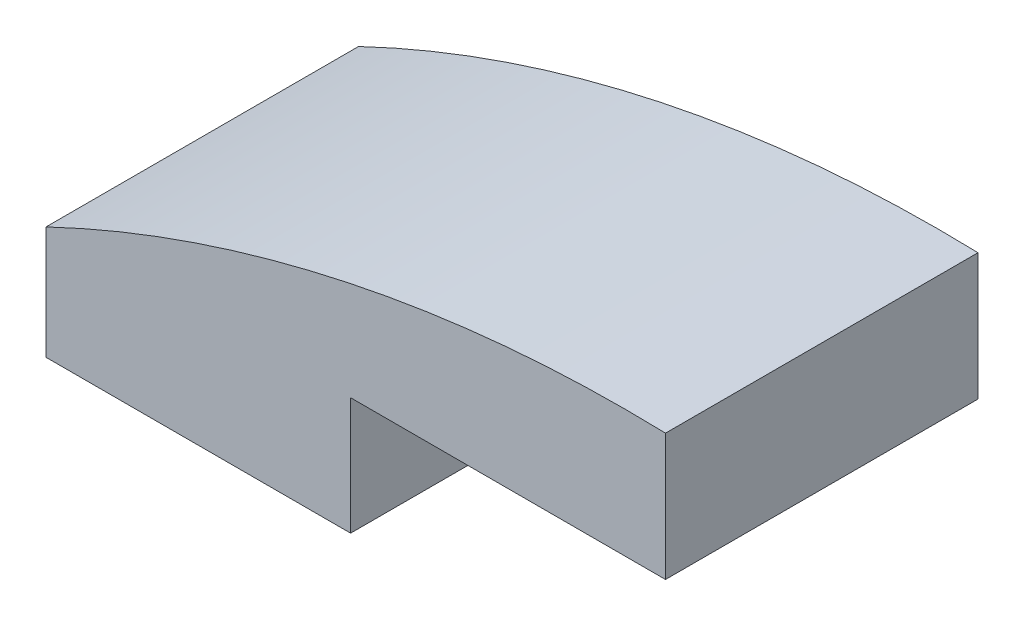
SolidWorks part; units mm, degrees
ref_plane "Front Plane" through (0, 0, 0) normal (0, 0, 1) x (1, 0, 0)
ref_plane "Top Plane" through (0, 0, 0) normal (0, 1, 0) x (1, 0, 0)
ref_plane "Right Plane" through (0, 0, 0) normal (1, 0, 0) x (0, 0, -1)
sketch "Sketch1" plane through (0, 0, 0) normal (0, 0, 1) x (1, 0, 0)
  line L0 (-7.9, -0.6252) -> (-7.9, 2.2297)
  line L12 (7.9, 5.5409) -> (7.9, 2.3409)
  line L15 (-0.2, -0.6252) -> (-7.9, -0.6252)
  line L17 (7.9, 2.3409) -> (-0.2, 2.3409)
  line L18 (-0.2, 2.3409) -> (-0.2, -0.6252)
  arc A0 (-7.9, 2.2297) -> (7.9, 5.5409) centre (6.7535, -28.3397) cw
  dimension "D3" = 3.2
extrude "Boss-Extrude1" add sketch "Sketch1" along normal mid plane 7.9
ref_plane "Plane1" through (0, -0.6252, 0) normal (0, -1, 0) x (-1, 0, 0)
shell "Shell1" thickness 1.2 removed face at (-4.05, -0.6252, 0) removed face at (3.85, 2.3409, 0)
ref_plane "Plane7" through (0, 2.3409, 0) normal (0, -1, 0) x (-1, 0, 0)
ref_plane "Plane8" [suppressed] through (0, 1.0372, 0) normal (0, -1, 0) x (-1, 0, 0)
sketch "Sketch7" [suppressed] plane through (0, 1.0372, 0) normal (0, -1, 0) x (-1, 0, 0)
  line L0 (7.9, 3.95) -> (0, -3.95)
  line L3 (7.9, 3.95) -> (7.9, -3.95)
  line L4 (7.9, -3.95) -> (0, -3.95)
extrude "Cut-Extrude4" [suppressed] cut sketch "Sketch7" against normal up to next
ref_plane "Plane9" through (0, 0, 0) normal (-1, 0, 0) x (0, 0, 1)
ref_plane "Plane10" through (0, 2.3409, 0) normal (0, -1, 0) x (-1, 0, 0)
sketch "Sketch8" plane through (0, 2.3409, 0) normal (0, -1, 0) x (-1, 0, 0)
  line L0 (-3.85, 3.95) -> (-3.85, -3.95) construction
  line L1 (0.2, 3.95) -> (-7.9, 3.95) construction
  line L2 (0.2, -3.95) -> (-7.9, -3.95) construction
  circle A0 centre (-3.85, 0) radius 2.3
  circle A1 centre (-3.85, 0) radius 2
  dimension "D1" = 4.6
  dimension "D2" = 4
extrude "Boss-Extrude2" add sketch "Sketch8" against normal up to next from offset 1.2
ref_plane "Plane11" through (0, -0.6252, 0) normal (0, -1, 0) x (-1, 0, 0)
sketch "Sketch9" plane through (0, -0.6252, 0) normal (0, -1, 0) x (-1, 0, 0)
  line L0 (1.4, 2.75) -> (6.7, -2.75) construction
  line L1 (6.7, 2.75) -> (1.4, -2.75) construction
  circle A0 centre (4.05, 0) radius 2.25
  circle A1 centre (4.05, 0) radius 2
  dimension "D1" = 4.5
  dimension "D2" = 4
extrude "Boss-Extrude3" add sketch "Sketch9" against normal up to next from offset 1.2
sketch "Sketch10" plane through (0, 0, -3.95) normal (0, 0, -1) x (-1, 0, 0)
  line L0 (-7.9, 2.3409) -> (-7.7606, 2.3409)
  line L1 (0.2, 2.3409) -> (-7.9, 2.3409) construction
  line L2 (-7.7606, 2.3409) -> (-7.7606, 5.5453)
  line L3 (-7.7606, 5.5453) -> (-7.9, 5.5409)
  line L4 (-7.9, 5.5409) -> (-7.9, 2.3409)
  arc A0 (7.9, 2.2297) -> (-7.9, 5.5409) centre (-6.7535, -28.3397) ccw construction
extrude "Cut-Extrude5" cut sketch "Sketch10" against normal through all body kept at (-7.9, -0.6252, -3.95)
